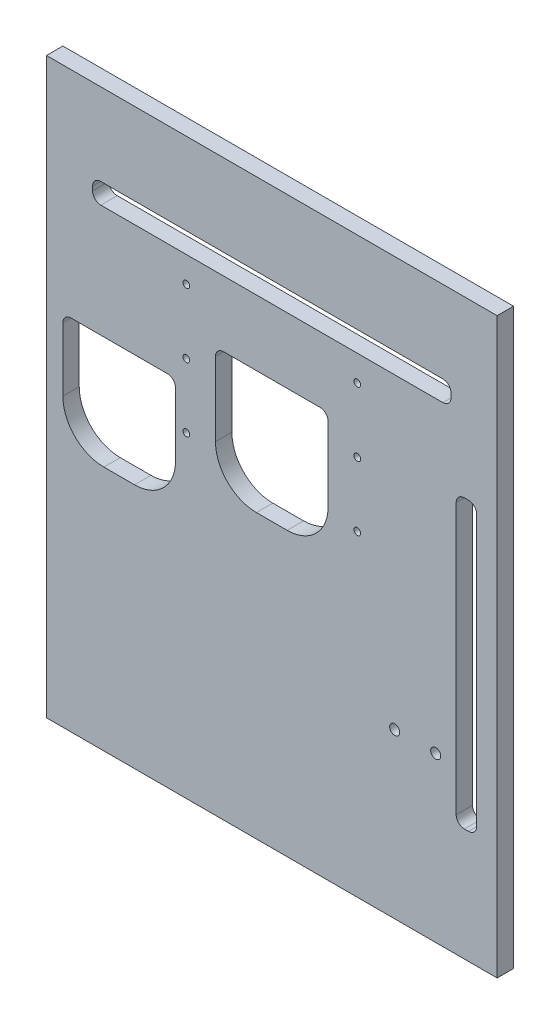
SolidWorks part; units mm, degrees
ref_plane "Front" through (0, 0, 0) normal (0, 0, 1) x (1, 0, 0)
ref_plane "Top" through (0, 0, 0) normal (0, 1, 0) x (1, 0, 0)
ref_plane "Right" through (0, 0, 0) normal (1, 0, 0) x (0, 0, -1)
sketch "Esquisse1" plane through (0, 0, 0) normal (0, 0, 1) x (1, 0, 0)
  line L1 (0, 0) -> (220, 0)
  line L2 (0, 0) -> (0, 280)
  line L3 (0, 280) -> (220, 280)
  line L4 (220, 0) -> (220, 280)
  dimension "D1" = 220
  dimension "D2" = 280
extrude "Boss.-Extru.1" add sketch "Esquisse1" along normal blind 8
sketch "Esquisse2" plane through (0, 0, 0) normal (0, -1, 0) x (1, 0, 0)
  line L0 (0, 4) -> (220, 4) construction
  line L1 (0, 8) -> (0, 0) construction
  line L2 (220, 8) -> (220, 0) construction
  line L3 (110, 4) -> (110, 28.0559) construction
  circle A0 centre (110, 4) radius 2
  circle A1 centre (210, 4) radius 2
  circle A2 centre (10, 4) radius 2
  dimension "D1" = 4
  dimension "D2" = 100
extrude "Enlèv. mat.-Extru.1" cut sketch "Esquisse2" against normal blind 10
sketch "Esquisse3" plane through (0, 0, 8) normal (0, 0, 1) x (1, 0, 0)
  line L0 (110, 0) -> (110, 280) construction
  line L1 (0, 0) -> (220, 0) construction
  line L2 (220, 280) -> (0, 280) construction
  line L3 (82.5, 198) -> (137.5, 198)
  line L4 (137.5, 198) -> (137.5, 138)
  line L5 (137.5, 138) -> (82.5, 138)
  line L6 (82.5, 198) -> (82.5, 138)
  line L8 (8, 175) -> (63, 175)
  line L9 (8, 175) -> (8, 120)
  line L10 (8, 120) -> (63, 120)
  line L11 (63, 175) -> (63, 120)
  line L12 (200, 55) -> (210, 55)
  line L13 (200, 55) -> (200, 195)
  line L14 (200, 195) -> (210, 195)
  line L15 (210, 55) -> (210, 195)
  point P11 (110, 138)
  point P12 (110, 198)
  dimension "D1" = 60
  dimension "D2" = 55
  dimension "D3" = 138
  dimension "D4" = 55
  dimension "D5" = 47
  dimension "D6" = 55
  dimension "D7" = 120
  dimension "D8" = 140
  dimension "D9" = 55
  dimension "D10" = 90
  dimension "D11" = 10
extrude "Enlèv. mat.-Extru.2" cut sketch "Esquisse3" against normal through all both and the other way through all
sketch "Esquisse5" plane through (0, 0, 8) normal (0, 0, 1) x (1, 0, 0)
  line L0 (110, 230) -> (110, 0) construction
  line L1 (22.5, 240) -> (197.5, 240)
  line L2 (22.5, 240) -> (22.5, 230)
  line L3 (22.5, 230) -> (197.5, 230)
  line L4 (197.5, 240) -> (197.5, 230)
  line L5 (0, 0) -> (220, 0) construction
  dimension "D1" = 175
  dimension "D2" = 10
  dimension "D3" = 230
extrude "Enlèv. mat.-Extru.3" cut sketch "Esquisse5" against normal through all both and the other way through all
sketch "Esquisse6" plane through (0, 0, 8) normal (0, 0, 1) x (1, 0, 0)
  line L0 (170, 80) -> (190, 80) construction
  line L1 (0, 0) -> (220, 0) construction
  line L2 (137.5, 138) -> (82.5, 138) construction
  circle A0 centre (190, 80) radius 2.45
  circle A1 centre (170, 80) radius 2.45
  point P8 (110, 138)
  dimension "D1" = 4.9
  dimension "D3" = 80
  dimension "D2" = 20
  dimension "D4" = 60
extrude "Enlèv. mat.-Extru.4" cut sketch "Esquisse6" against normal through all both and the other way through all
sketch "Esquisse7" plane through (0, 0, 8) normal (0, 0, 1) x (1, 0, 0)
  line L0 (110, 0) -> (110, 280) construction
  line L1 (0, 0) -> (220, 0) construction
  line L2 (220, 280) -> (0, 280) construction
  line L3 (68.285, 186) -> (68.285, 217.4) construction
  line L4 (68.285, 186) -> (110, 186) construction
  line L5 (151.715, 186) -> (151.715, 217.4) construction
  circle A0 centre (68.285, 217.4) radius 1.65
  circle A1 centre (68.285, 186) radius 1.65
  circle A2 centre (68.285, 154.6) radius 1.65
  circle A3 centre (151.715, 154.6) radius 1.65
  circle A4 centre (151.715, 186) radius 1.65
  circle A5 centre (151.715, 217.4) radius 1.65
  dimension "D1" = 31.4
  dimension "D2" = 3.3
  dimension "D3" = 83.43
  dimension "D4" = 186
extrude "Enlèv. mat.-Extru.5" cut sketch "Esquisse7" against normal through all both and the other way through all
fillet "Congé1" radius 20 4 edges at (137.5, 138, 4) (82.5, 138, 4) (63, 120, 4) (8, 120, 4)
fillet "Congé2" radius 4 12 edges at (137.5, 198, 4) (82.5, 198, 4) (197.5, 230, 4) (197.5, 240, 4) (22.5, 240, 4) (22.5, 230, 4) (63, 175, 4) (8, 175, 4) (200, 195, 4) (210, 195, 4) (210, 55, 4) (200, 55, 4)
